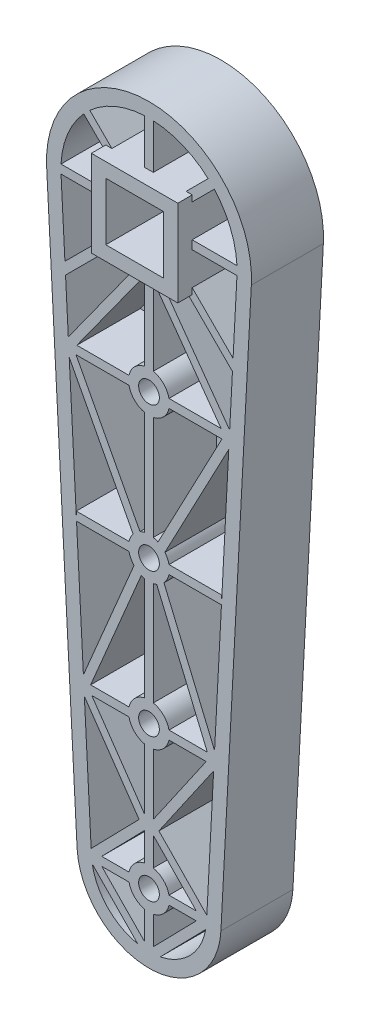
SolidWorks part; units mm, degrees
ref_plane "Front Plane" through (0, 0, 0) normal (0, 0, 1) x (1, 0, 0)
ref_plane "Top Plane" through (0, 0, 0) normal (0, 1, 0) x (1, 0, 0)
ref_plane "Right Plane" through (0, 0, 0) normal (1, 0, 0) x (0, 0, -1)
sketch "Sketch1" plane through (0, 0, 0) normal (0, 0, 1) x (1, 0, 0)
  line L0 (0, 0) -> (0, -200) construction
  line L1 (-10, 10) -> (10, 10)
  line L2 (-10, 10) -> (-10, -10)
  line L3 (-10, -10) -> (10, -10)
  line L4 (10, 10) -> (10, -10)
  line L5 (-10, 10) -> (10, -10) construction
  line L6 (-10, -10) -> (10, 10) construction
  line L7 (-35.5252, -1.881) -> (-24.965, -201.3219)
  line L8 (24.965, -201.3219) -> (35.5252, -1.881)
  circle A0 centre (0, -200) radius 10 construction
  circle A1 centre (0, -200) radius 25 construction
  circle A2 centre (0, 0) radius 35.575 construction
  arc A3 (-35.5252, -1.881) -> (35.5252, -1.881) centre (0, 0) cw
  arc A4 (-24.965, -201.3219) -> (24.965, -201.3219) centre (0, -200) ccw
  point P0 (0, 0)
  dimension "D3" = 20
  dimension "D4" = 15
  dimension "D5" = 71.15
  dimension "D1" = 20
  dimension "D2" = 200
extrude "Boss-Extrude1" add sketch "Sketch1" along normal blind 25
sketch "Sketch2" plane through (0, 0, 25) normal (0, 0, 1) x (1, 0, 0)
  line L4 (-30.5322, -1.6167) -> (-19.972, -201.0575)
  line L5 (19.972, -201.0575) -> (30.5322, -1.6167)
  line L6 (-30.5322, -1.6167) -> (-19.972, -201.0575)
  line L7 (19.972, -201.0575) -> (30.5322, -1.6167)
  line L26 (15, -15) -> (15, 15)
  line L27 (-15, -15) -> (15, -15)
  line L28 (-15, 15) -> (-15, -15)
  line L29 (15, 15) -> (-15, 15)
  line L30 (15, -15) -> (15, 15)
  line L31 (-15, -15) -> (15, -15)
  line L32 (-15, 15) -> (-15, -15)
  line L33 (15, 15) -> (-15, 15)
  arc A4 (30.5322, -1.6167) -> (-30.5322, -1.6167) centre (0, 0) ccw
  arc A5 (-19.972, -201.0575) -> (19.972, -201.0575) centre (0, -200) ccw
  arc A6 (30.5322, -1.6167) -> (-30.5322, -1.6167) centre (0, 0) ccw
  arc A7 (-19.972, -201.0575) -> (19.972, -201.0575) centre (0, -200) ccw
  dimension "D1" = 5
  dimension "D2" = 5
extrude "Cut-Extrude1" cut sketch "Sketch2" against normal offset from surface (22 mm away) 3 up to face at (0, -98.157, 0)
sketch "Sketch3" plane through (0, 0, 25) normal (0, 0, 1) x (1, 0, 0)
  line L0 (-10, 10) -> (-21.6198, 21.6198) construction
  line L1 (10, 10) -> (21.6198, 21.6198) construction
  line L2 (19.972, -201.0575) -> (30.5322, -1.6167) construction
  line L4 (-30.5322, -1.6167) -> (-19.972, -201.0575) construction
  line L6 (-10, 0) -> (-30.575, 0) construction
  line L8 (10, 0) -> (30.575, 0) construction
  line L9 (10, -10) -> (10, 10) construction
  line L10 (0, 10) -> (0, 30.575) construction
  line L11 (10, 10) -> (-10, 10) construction
  line L12 (0, -10) -> (0, -220) construction
  line L13 (-10, -10) -> (10, -10) construction
  line L14 (-10, 10) -> (-10, -10) construction
  line L19 (-8.9393, 11.0607) -> (-20.5591, 22.6805)
  line L20 (-30.575, 1.5) -> (-10, 1.5)
  line L21 (-1.5, 30.575) -> (1.5, 30.575)
  line L22 (-1.5, 30.575) -> (-1.5, 10)
  line L23 (-1.5, 10) -> (1.5, 10)
  line L24 (1.5, 30.575) -> (1.5, 10)
  line L25 (-1.5, 30.575) -> (1.5, 10) construction
  line L26 (-1.5, 10) -> (1.5, 30.575) construction
  line L27 (30.575, -1.5) -> (10, -1.5)
  line L28 (30.575, -1.5) -> (30.575, 1.5)
  line L29 (30.575, 1.5) -> (10, 1.5)
  line L30 (10, -1.5) -> (10, 1.5)
  line L31 (30.575, -1.5) -> (10, 1.5) construction
  line L32 (30.575, 1.5) -> (10, -1.5) construction
  line L33 (-30.575, 1.5) -> (-30.575, -1.5)
  line L34 (-30.575, -1.5) -> (-10, -1.5)
  line L35 (-10, 1.5) -> (-10, -1.5)
  line L36 (-30.575, 1.5) -> (-10, -1.5) construction
  line L37 (-30.575, -1.5) -> (-10, 1.5) construction
  line L38 (-1.5, -220) -> (1.5, -220)
  line L39 (-1.5, -220) -> (-1.5, -10)
  line L40 (-1.5, -10) -> (1.5, -10)
  line L41 (1.5, -220) -> (1.5, -10)
  line L42 (-1.5, -220) -> (1.5, -10) construction
  line L43 (-1.5, -10) -> (1.5, -220) construction
  line L44 (11.0607, 8.9393) -> (22.6805, 20.5591)
  line L45 (8.9393, -11.0607) -> (28.9715, -31.0928)
  line L46 (-11.0607, -8.9393) -> (-31.0928, -28.9715)
  line L47 (-11.0607, 8.9393) -> (-22.6805, 20.5591)
  line L48 (8.9393, 11.0607) -> (20.5591, 22.6805)
  line L49 (11.0607, -8.9393) -> (31.0928, -28.9715)
  line L50 (-8.9393, -11.0607) -> (-28.9715, -31.0928)
  line L51 (-8.9393, 11.0607) -> (-11.0607, 8.9393)
  line L52 (-20.5591, 22.6805) -> (-22.6805, 20.5591)
  line L53 (11.0607, 8.9393) -> (8.9393, 11.0607)
  line L54 (22.6805, 20.5591) -> (20.5591, 22.6805)
  line L55 (8.9393, -11.0607) -> (11.0607, -8.9393)
  line L56 (28.9715, -31.0928) -> (31.0928, -28.9715)
  line L57 (-11.0607, -8.9393) -> (-8.9393, -11.0607)
  line L58 (-31.0928, -28.9715) -> (-28.9715, -31.0928)
  arc A0 (30.5322, -1.6167) -> (-30.5322, -1.6167) centre (0, 0) ccw construction
  arc A1 (30.5322, -1.6167) -> (-30.5322, -1.6167) centre (0, 0) ccw construction
  arc A2 (-19.972, -201.0575) -> (19.972, -201.0575) centre (0, -200) ccw construction
  point P12 (0, -190)
  point P13 (0, -210)
  point P14 (0, -220)
  point P30 (-20.2875, 0)
  point P52 (0, -115)
  point P55 (0, 20.2875)
  point P60 (20.2875, 0)
  dimension "D1" = 3
  dimension "D2" = 1.5
  dimension "D3" = 1.5
extrude "Boss-Extrude3" add sketch "Sketch3" against normal up to surface (22 mm away) up to face at (0, -98.0248, 3)
sketch "Sketch6" plane through (0, 0, 25) normal (0, 0, 1) x (1, 0, 0)
  line L0 (-32.8926, -51.6015) -> (32.8926, -51.6015) construction
  line L1 (-35.5252, -1.881) -> (-24.965, -201.3219) construction
  line L2 (24.965, -201.3219) -> (35.5252, -1.881) construction
  line L3 (30.2451, -101.6015) -> (-30.2451, -101.6015) construction
  line L4 (27.5977, -151.6015) -> (-27.5977, -151.6015) construction
  line L5 (-1.5, -15) -> (-27.8856, -51.6015) construction
  line L6 (-28.9715, -31.0928) -> (-19.972, -201.0575) construction
  line L7 (-27.8856, -51.6015) -> (-1.5, -101.6015) construction
  line L8 (-1.5, -15) -> (-1.5, -219.9437) construction
  line L9 (-1.5, -101.6015) -> (-22.5907, -151.6015) construction
  line L10 (-28.9715, -31.0928) -> (-19.972, -201.0575) construction
  line L11 (-22.5907, -151.6015) -> (-1.5, -182.1458) construction
  line L12 (-1.5, -182.1458) -> (1.5, -182.1458) construction
  line L13 (1.5, -182.1458) -> (22.5907, -151.6015) construction
  line L14 (19.972, -201.0575) -> (28.9715, -31.0928) construction
  line L15 (22.5907, -151.6015) -> (1.5, -101.6015) construction
  line L16 (1.5, -15) -> (1.5, -219.9437) construction
  line L17 (1.5, -101.6015) -> (27.8856, -51.6015) construction
  line L18 (27.8856, -51.6015) -> (1.5, -15) construction
  line L19 (-2.7168, -14.1228) -> (-29.6463, -51.4788)
  line L20 (-29.6463, -51.4788) -> (-3.1582, -101.6731)
  line L21 (-3.1582, -101.6731) -> (-24.2926, -151.7766)
  line L22 (-24.2926, -151.7766) -> (-2.7343, -182.9981)
  line L23 (2.7343, -182.9981) -> (24.2926, -151.7766)
  line L24 (24.2926, -151.7766) -> (3.1582, -101.6731)
  line L25 (3.1582, -101.6731) -> (29.6463, -51.4788)
  line L26 (29.6463, -51.4788) -> (2.7168, -14.1228)
  line L27 (-0.2832, -15.8772) -> (-26.1248, -51.7241)
  line L28 (-26.1248, -51.7241) -> (0.1582, -101.5298)
  line L29 (0.1582, -101.5298) -> (-20.8888, -151.4263)
  line L30 (-20.8888, -151.4263) -> (-0.2657, -181.2935)
  line L31 (0.2657, -181.2935) -> (20.8888, -151.4263)
  line L32 (20.8888, -151.4263) -> (-0.1582, -101.5298)
  line L33 (-0.1582, -101.5298) -> (26.1248, -51.7241)
  line L34 (26.1248, -51.7241) -> (0.2832, -15.8772)
  line L35 (-2.7168, -14.1228) -> (-0.2832, -15.8772)
  line L36 (-2.7343, -182.9981) -> (-0.2657, -181.2935)
  line L37 (2.7343, -182.9981) -> (0.2657, -181.2935)
  line L38 (2.7168, -14.1228) -> (0.2832, -15.8772)
  line L39 (-1.5, -182.1458) -> (-19.972, -201.0575) construction
  line L40 (-19.972, -201.0575) -> (-1.5, -219.9437) construction
  line L41 (-1.5, -219.9437) -> (1.5, -219.9437) construction
  line L42 (1.5, -219.9437) -> (19.972, -201.0575) construction
  line L43 (19.972, -201.0575) -> (1.5, -182.1458) construction
  line L44 (-2.5731, -181.0977) -> (-22.0695, -201.0582)
  line L45 (-22.0695, -201.0582) -> (-2.5724, -220.9925)
  line L46 (2.5724, -220.9925) -> (22.0695, -201.0582)
  line L47 (22.0695, -201.0582) -> (2.5731, -181.0977)
  line L48 (-0.4269, -183.1939) -> (-17.8745, -201.0568)
  line L49 (-17.8745, -201.0568) -> (-0.4276, -218.8948)
  line L50 (0.4276, -218.8948) -> (17.8745, -201.0568)
  line L51 (17.8745, -201.0568) -> (0.4269, -183.1939)
  line L52 (-2.5731, -181.0977) -> (-0.4269, -183.1939)
  line L53 (-2.5724, -220.9925) -> (-0.4276, -218.8948)
  line L54 (2.5724, -220.9925) -> (0.4276, -218.8948)
  line L55 (2.5731, -181.0977) -> (0.4269, -183.1939)
  line L56 (-1.5, -15) -> (-1.5, -219.9437) construction
  line L57 (1.5, -219.9437) -> (1.5, -15) construction
  point P74 (-5.0378, -182.1458)
  point P75 (0, 0)
  point P78 (0, 0)
  line M13 (-12.8787, -15) -> (-1.5, -15)
  line M14 (-1.5, -15) -> (-1.5, -219.9437)
  line M16 (1.5, -219.9437) -> (1.5, -15)
  line M17 (1.5, -15) -> (12.8787, -15)
  line M19 (28.9715, -31.0928) -> (19.972, -201.0575)
  line M21 (-19.972, -201.0575) -> (-28.9715, -31.0928)
  dimension "D1" = 50
  dimension "D2" = 50
  dimension "D7" = 101.049
  dimension "D3" = 1.5
  dimension "D4" = 1.5
  dimension "D5" = 1.5
  dimension "D6" = 1.5
extrude "Boss-Extrude4" add sketch "Sketch6" against normal up to surface (22 mm away) contours L34 L33 L32 L31 L23 L24 L25 L26 M16 M19 M17 | L30 L29 L28 L27 L19 L20 L21 L22 M14 M13 M21 | L44 L45 L53 L49 L48 L52 | L46 L47 L55 L51 L50 L54 region at (-2.4246, -16.6924, 25) region at (15.3091, -75.8456, 25) up to face at (-13.6768, -97.1156, 3)
sketch "Sketch7" plane through (0, 0, 25) normal (0, 0, 1) x (1, 0, 0)
  line L0 (-10, 10) -> (-10, -10) construction
  line L1 (-10, -10) -> (10, -10) construction
  line L2 (10, -10) -> (10, 10) construction
  line L3 (10, 10) -> (-10, 10) construction
  line L4 (-10, 10) -> (-10, -10)
  line L5 (-10, -10) -> (10, -10)
  line L6 (10, -10) -> (10, 10)
  line L7 (10, 10) -> (-10, 10)
  line L9 (15, -15) -> (-15, -15)
  line L10 (15, -15) -> (15, 15)
  line L11 (15, 15) -> (-15, 15)
  line L12 (-15, -15) -> (-15, 15)
  line L13 (15, -15) -> (-15, 15) construction
  line L14 (15, 15) -> (-15, -15) construction
  line L15 (-15, 12.8787) -> (-15, 1.5) construction
  line L16 (-1.5, 15) -> (-12.8787, 15) construction
  point P2 (0, 0)
extrude "Boss-Extrude5" add sketch "Sketch7" along normal blind 5
sketch "Sketch8" plane through (0, 0, 0) normal (0, 0, -1) x (-1, 0, 0)
  line L0 (0, 0) -> (0, -225) construction
  line L1 (-20.8888, -151.4263) -> (20.8888, -151.4263) construction
  line L2 (-3.1582, -101.6731) -> (3.1582, -101.6731) construction
  line L3 (17.8745, -201.0568) -> (-17.8745, -201.0568) construction
  line L4 (-26.1248, -51.7241) -> (26.1248, -51.7241) construction
  arc A0 (-24.965, -201.3219) -> (24.965, -201.3219) centre (0, -200) ccw construction
  circle A4 centre (0, -101.6731) radius 3.6
  circle A5 centre (0, -151.4263) radius 3.6
  circle A6 centre (0, -201.0568) radius 3.6
  circle A7 centre (0, -51.7241) radius 3.6
  point P8 (0, -151.4263)
  dimension "D1" = 7.2
extrude "Cut-Extrude2" cut sketch "Sketch8" against normal through all
sketch "Sketch9" plane through (0, 0, 3) normal (0, 0, 1) x (1, 0, 0)
  circle A4 centre (0, -51.7241) radius 3.6
  circle A5 centre (0, -101.6731) radius 3.6
  circle A6 centre (0, -151.4263) radius 3.6
  circle A7 centre (0, -201.0568) radius 3.6
  arc A8 (-1.5, -48.4514) -> (-1.5, -54.9967) centre (0, -51.7241) ccw construction
  circle A9 centre (0, -51.7241) radius 7.1
  circle A10 centre (0, -101.6731) radius 7.1
  circle A11 centre (0, -151.4263) radius 7.1
  circle A12 centre (0, -201.0568) radius 7.1
  circle A13 centre (0, -51.7241) radius 0.1
  circle A14 centre (0, -101.6731) radius 0.1
  circle A15 centre (0, -151.4263) radius 0.1
  circle A16 centre (0, -201.0568) radius 0.1
  line M5 (1.5, -17.5651) -> (1.5, -48.4514)
  arc M6 (1.5, -48.4514) -> (1.5, -54.9967) centre (0, -51.7241) cw
  line M7 (1.5, -54.9967) -> (1.5, -98.3875)
  line M8 (1.5, -98.3875) -> (26.1248, -51.7241)
  dimension "D1" = 3.5
  dimension "D2" = 3.5
extrude "Boss-Extrude6" add sketch "Sketch9" along normal up to surface (22 mm away) contours A9 M7 M5 M6 | A10 A5 M7 M8 | A9 A4 M5 M7 | A10 M8 M7 | A11 A6 | A12 A7 region at (4.1409, -51.7241, 3) region at (-3.766, -51.7241, 3) region at (2.0487, -96.1175, 3) region at (1.2992, -96.5604, 3) region at (-6.8992, -151.4263, 3) region at (-6.8992, -201.0568, 3) up to face at (0, -98.157, 25)
sketch "Sketch10" plane through (0, 0, 25) normal (0, 0, 1) x (1, 0, 0)
  line L0 (-3.6, -51.7241) -> (-26.1248, -51.7241) construction
  line L1 (3.6, -51.7241) -> (26.1248, -51.7241) construction
  line L2 (-3.6, -101.6731) -> (-25.2343, -101.6731) construction
  line L3 (-27.6964, -55.1739) -> (-22.7722, -148.1724) construction
  line L4 (3.6, -101.6731) -> (25.2343, -101.6731) construction
  line L5 (22.7722, -148.1724) -> (27.6964, -55.1739) construction
  line L6 (-3.6, -151.4263) -> (-20.8888, -151.4263) construction
  line L7 (3.6, -151.4263) -> (20.8888, -151.4263) construction
  line L8 (-3.6, -201.0568) -> (-17.8745, -201.0568) construction
  line L9 (3.6, -201.0568) -> (17.8745, -201.0568) construction
  line L10 (-3.6, -50.2241) -> (-26.1248, -50.2241)
  line L11 (3.6, -53.2241) -> (26.1248, -53.2241)
  line L12 (-3.6, -100.1731) -> (-25.2343, -100.1731)
  line L13 (3.6, -103.1731) -> (25.2343, -103.1731)
  line L14 (-3.6, -149.9263) -> (-20.8888, -149.9263)
  line L15 (3.6, -152.9263) -> (20.8888, -152.9263)
  line L16 (-3.6, -199.5568) -> (-17.8745, -199.5568)
  line L17 (3.6, -202.5568) -> (17.8745, -202.5568)
  line L18 (-3.6, -53.2241) -> (-26.1248, -53.2241)
  line L19 (3.6, -50.2241) -> (26.1248, -50.2241)
  line L20 (-3.6, -103.1731) -> (-25.2343, -103.1731)
  line L21 (3.6, -100.1731) -> (25.2343, -100.1731)
  line L22 (-3.6, -152.9263) -> (-20.8888, -152.9263)
  line L23 (3.6, -149.9263) -> (20.8888, -149.9263)
  line L24 (-3.6, -202.5568) -> (-17.8745, -202.5568)
  line L25 (3.6, -199.5568) -> (17.8745, -199.5568)
  line L26 (-3.6, -50.2241) -> (-3.6, -53.2241)
  line L27 (-26.1248, -50.2241) -> (-26.1248, -53.2241)
  line L28 (3.6, -53.2241) -> (3.6, -50.2241)
  line L29 (26.1248, -53.2241) -> (26.1248, -50.2241)
  line L30 (-3.6, -100.1731) -> (-3.6, -103.1731)
  line L31 (-25.2343, -100.1731) -> (-25.2343, -103.1731)
  line L32 (3.6, -103.1731) -> (3.6, -100.1731)
  line L33 (25.2343, -103.1731) -> (25.2343, -100.1731)
  line L34 (-3.6, -149.9263) -> (-3.6, -152.9263)
  line L35 (-20.8888, -149.9263) -> (-20.8888, -152.9263)
  line L36 (3.6, -152.9263) -> (3.6, -149.9263)
  line L37 (20.8888, -152.9263) -> (20.8888, -149.9263)
  line L38 (-3.6, -199.5568) -> (-3.6, -202.5568)
  line L39 (-17.8745, -199.5568) -> (-17.8745, -202.5568)
  line L40 (3.6, -202.5568) -> (3.6, -199.5568)
  line L41 (17.8745, -202.5568) -> (17.8745, -199.5568)
  circle A0 centre (0, -51.7241) radius 3.6 construction
  circle A1 centre (0, -101.6731) radius 3.6 construction
  circle A2 centre (0, -151.4263) radius 3.6 construction
  circle A3 centre (0, -201.0568) radius 3.6 construction
  dimension "D1" = 1.5
  dimension "D2" = 1.5
extrude "Boss-Extrude7" add sketch "Sketch10" against normal up to surface (22 mm away) up to face at (6.8119, -60.4535, 3)
sketch "Sketch11" plane through (0, 0, 0) normal (0, 0, -1) x (-1, 0, 0)
  circle A0 centre (0, -51.7241) radius 6.25
  circle A1 centre (0, -101.6731) radius 6.25
  circle A2 centre (0, -151.4263) radius 6.25
  circle A3 centre (0, -201.0568) radius 6.25
  dimension "D1" = 12.5
extrude "Cut-Extrude3" cut sketch "Sketch11" against normal blind 1.2
chamfer "Chamfer1" distance 1 angle 45 4 edges at (-3.6, -201.0568, 1.2) (-3.6, -151.4263, 1.2) (-3.6, -101.6731, 1.2) (-3.6, -51.7241, 1.2)
